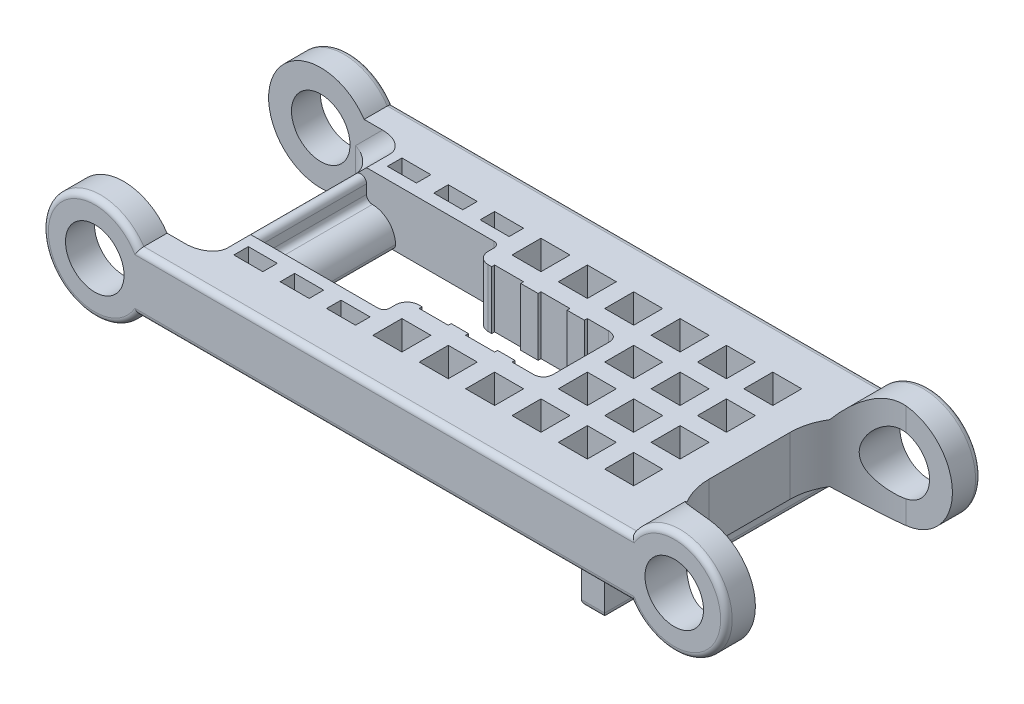
SolidWorks part; units mm, degrees
other "Markup1"
sketch "Sketch14" plane through (109, 9, 22) normal (0.0604, 0.9942, 0.0886) x (0.9982, -0.0602, -0.0054)
ref_plane "Front Plane" through (0, 0, 0) normal (0, 0, 1) x (1, 0, 0)
ref_plane "Top Plane" through (0, 0, 0) normal (0, 1, 0) x (1, 0, 0)
ref_plane "Right Plane" through (0, 0, 0) normal (1, 0, 0) x (0, 0, -1)
sketch "Sketch1" plane through (0, 0, 0) normal (0, 0, 1) x (1, 0, 0)
  line L0 (0, 0) -> (60, 0) construction
  line L1 (0, 9) -> (60, 9) construction
  line L2 (0, -9) -> (60, -9) construction
  line L3 (30, 0) -> (30, -9) construction
  line L4 (50, 5) -> (50, -5)
  line L6 (7.4833, -5) -> (7.4833, 5) construction
  line L7 (50, 5) -> (7.4833, 5)
  line L8 (50, 5) -> (50, -5)
  line L9 (50, -5) -> (7.4833, -5)
  arc A0 (0, 9) -> (0, -9) centre (0, 0) ccw construction
  arc A1 (60, -9) -> (60, 9) centre (60, 0) ccw construction
  circle A2 centre (0, 0) radius 9
  circle A3 centre (0, 0) radius 5.05
  point P3 (30, 0)
  dimension "D3" = 10.1
  dimension "D1" = 18
  dimension "D2" = 5
  dimension "D4" = 50
  dimension "D6" = 5
extrude "Boss-Extrude1" add sketch "Sketch1" along normal mid plane 44
sketch "Sketch4" plane through (0, 0, 0) normal (0, 1, 0) x (1, 0, 0)
  line L0 (-9, 22) -> (-9, -22) construction
  line L1 (9, 17) -> (-9, 17)
  line L2 (9, 17) -> (9, -17)
  line L3 (9, -17) -> (-9, -17)
  line L4 (-9, 17) -> (-9, -17)
  line L5 (9, 17) -> (-9, -17) construction
  line L6 (9, -17) -> (-9, 17) construction
  line L7 (7.4833, 22) -> (-9, 22) construction
  point P0 (0, 0)
  dimension "D1" = 5
extrude "Cut-Extrude2" cut sketch "Sketch4" against normal through all both and the other way through all
mirror "Mirror2" about plane through (50, 0, 22) normal (1, 0, 0) of "Boss-Extrude1", "Cut-Extrude2"
sketch "Sketch5" plane through (0, 5, 0) normal (0, 1, 0) x (1, 0, 0)
  line L105 (24.5, 9.5) -> (29.5, 9.5)
  line L106 (16.5, 14.5) -> (21.5, 14.5)
  line L107 (16.5, 14.5) -> (16.5, 9.5)
  line L108 (16.5, 9.5) -> (21.5, 9.5)
  line L125 (21.5, 14.5) -> (21.5, 9.5)
  line L126 (84.5, -15.5) -> (84.5, 15.5)
  line L127 (24.5, 14.5) -> (29.5, 14.5)
  line L129 (24.5, 14.5) -> (24.5, 9.5)
  line L130 (29.5, 14.5) -> (29.5, 9.5)
  line L131 (32.5, 9.5) -> (37.5, 9.5)
  line L132 (32.5, 14.5) -> (37.5, 14.5)
  line L133 (32.5, 14.5) -> (32.5, 9.5)
  line L134 (37.5, 14.5) -> (37.5, 9.5)
  line L137 (84.5, -15.5) -> (84.5, 15.5)
  line L143 (40.5, 9.5) -> (45.5, 9.5)
  line L144 (40.5, 14.5) -> (45.5, 14.5)
  line L145 (40.5, 14.5) -> (40.5, 9.5)
  line L146 (45.5, 14.5) -> (45.5, 9.5)
  line L147 (48.5, 9.5) -> (53.5, 9.5)
  line L148 (48.5, 14.5) -> (53.5, 14.5)
  line L149 (48.5, 14.5) -> (48.5, 9.5)
  line L150 (53.5, 14.5) -> (53.5, 9.5)
  line L151 (56.5, 9.5) -> (61.5, 9.5)
  line L152 (56.5, 14.5) -> (61.5, 14.5)
  line L153 (56.5, 14.5) -> (56.5, 9.5)
  line L154 (61.5, 14.5) -> (61.5, 9.5)
  line L155 (64.5, 9.5) -> (69.5, 9.5)
  line L156 (64.5, 14.5) -> (69.5, 14.5)
  line L157 (64.5, 14.5) -> (64.5, 9.5)
  line L158 (69.5, 14.5) -> (69.5, 9.5)
  line L159 (72.5, 9.5) -> (77.5, 9.5)
  line L160 (72.5, 14.5) -> (77.5, 14.5)
  line L161 (72.5, 14.5) -> (72.5, 9.5)
  line L162 (77.5, 14.5) -> (77.5, 9.5)
  line L163 (80.5, 9.5) -> (85.5, 9.5)
  line L164 (80.5, 14.5) -> (85.5, 14.5)
  line L165 (80.5, 14.5) -> (80.5, 9.5)
  line L166 (85.5, 14.5) -> (85.5, 9.5)
  line L167 (24.5, 1.5) -> (29.5, 1.5)
  line L168 (24.5, 6.5) -> (29.5, 6.5)
  line L169 (24.5, 6.5) -> (24.5, 1.5)
  line L170 (29.5, 6.5) -> (29.5, 1.5)
  line L171 (32.5, 1.5) -> (37.5, 1.5)
  line L172 (32.5, 6.5) -> (37.5, 6.5)
  line L173 (32.5, 6.5) -> (32.5, 1.5)
  line L174 (37.5, 6.5) -> (37.5, 1.5)
  line L175 (40.5, 1.5) -> (45.5, 1.5)
  line L176 (40.5, 6.5) -> (45.5, 6.5)
  line L177 (40.5, 6.5) -> (40.5, 1.5)
  line L178 (45.5, 6.5) -> (45.5, 1.5)
  line L179 (48.5, 1.5) -> (53.5, 1.5)
  line L180 (48.5, 6.5) -> (53.5, 6.5)
  line L181 (48.5, 6.5) -> (48.5, 1.5)
  line L182 (53.5, 6.5) -> (53.5, 1.5)
  line L183 (56.5, 1.5) -> (61.5, 1.5)
  line L184 (56.5, 6.5) -> (61.5, 6.5)
  line L185 (56.5, 6.5) -> (56.5, 1.5)
  line L186 (61.5, 6.5) -> (61.5, 1.5)
  line L187 (64.5, 1.5) -> (69.5, 1.5)
  line L188 (64.5, 6.5) -> (69.5, 6.5)
  line L189 (64.5, 6.5) -> (64.5, 1.5)
  line L190 (69.5, 6.5) -> (69.5, 1.5)
  line L191 (72.5, 1.5) -> (77.5, 1.5)
  line L192 (72.5, 6.5) -> (77.5, 6.5)
  line L193 (72.5, 6.5) -> (72.5, 1.5)
  line L194 (77.5, 6.5) -> (77.5, 1.5)
  line L195 (80.5, 1.5) -> (85.5, 1.5)
  line L196 (80.5, 6.5) -> (85.5, 6.5)
  line L197 (80.5, 6.5) -> (80.5, 1.5)
  line L198 (85.5, 6.5) -> (85.5, 1.5)
  line L199 (24.5, -6.5) -> (29.5, -6.5)
  line L200 (24.5, -1.5) -> (29.5, -1.5)
  line L201 (24.5, -1.5) -> (24.5, -6.5)
  line L202 (29.5, -1.5) -> (29.5, -6.5)
  line L203 (32.5, -6.5) -> (37.5, -6.5)
  line L204 (32.5, -1.5) -> (37.5, -1.5)
  line L205 (32.5, -1.5) -> (32.5, -6.5)
  line L206 (37.5, -1.5) -> (37.5, -6.5)
  line L207 (40.5, -6.5) -> (45.5, -6.5)
  line L208 (40.5, -1.5) -> (45.5, -1.5)
  line L209 (40.5, -1.5) -> (40.5, -6.5)
  line L210 (45.5, -1.5) -> (45.5, -6.5)
  line L211 (48.5, -6.5) -> (53.5, -6.5)
  line L212 (48.5, -1.5) -> (53.5, -1.5)
  line L213 (48.5, -1.5) -> (48.5, -6.5)
  line L214 (53.5, -1.5) -> (53.5, -6.5)
  line L215 (56.5, -6.5) -> (61.5, -6.5)
  line L216 (56.5, -1.5) -> (61.5, -1.5)
  line L217 (56.5, -1.5) -> (56.5, -6.5)
  line L218 (61.5, -1.5) -> (61.5, -6.5)
  line L219 (64.5, -6.5) -> (69.5, -6.5)
  line L220 (64.5, -1.5) -> (69.5, -1.5)
  line L221 (64.5, -1.5) -> (64.5, -6.5)
  line L222 (69.5, -1.5) -> (69.5, -6.5)
  line L223 (72.5, -6.5) -> (77.5, -6.5)
  line L224 (72.5, -1.5) -> (77.5, -1.5)
  line L225 (72.5, -1.5) -> (72.5, -6.5)
  line L226 (77.5, -1.5) -> (77.5, -6.5)
  line L227 (80.5, -6.5) -> (85.5, -6.5)
  line L228 (80.5, -1.5) -> (85.5, -1.5)
  line L229 (80.5, -1.5) -> (80.5, -6.5)
  line L230 (85.5, -1.5) -> (85.5, -6.5)
  line L231 (24.5, -14.5) -> (29.5, -14.5)
  line L232 (24.5, -9.5) -> (29.5, -9.5)
  line L233 (24.5, -9.5) -> (24.5, -14.5)
  line L234 (29.5, -9.5) -> (29.5, -14.5)
  line L235 (32.5, -14.5) -> (37.5, -14.5)
  line L236 (32.5, -9.5) -> (37.5, -9.5)
  line L237 (32.5, -9.5) -> (32.5, -14.5)
  line L238 (37.5, -9.5) -> (37.5, -14.5)
  line L239 (40.5, -14.5) -> (45.5, -14.5)
  line L240 (40.5, -9.5) -> (45.5, -9.5)
  line L241 (40.5, -9.5) -> (40.5, -14.5)
  line L242 (45.5, -9.5) -> (45.5, -14.5)
  line L243 (48.5, -14.5) -> (53.5, -14.5)
  line L244 (48.5, -9.5) -> (53.5, -9.5)
  line L245 (48.5, -9.5) -> (48.5, -14.5)
  line L246 (53.5, -9.5) -> (53.5, -14.5)
  line L247 (56.5, -14.5) -> (61.5, -14.5)
  line L248 (56.5, -9.5) -> (61.5, -9.5)
  line L249 (56.5, -9.5) -> (56.5, -14.5)
  line L250 (61.5, -9.5) -> (61.5, -14.5)
  line L251 (64.5, -14.5) -> (69.5, -14.5)
  line L252 (64.5, -9.5) -> (69.5, -9.5)
  line L253 (64.5, -9.5) -> (64.5, -14.5)
  line L254 (69.5, -9.5) -> (69.5, -14.5)
  line L255 (72.5, -14.5) -> (77.5, -14.5)
  line L256 (72.5, -9.5) -> (77.5, -9.5)
  line L257 (72.5, -9.5) -> (72.5, -14.5)
  line L258 (77.5, -9.5) -> (77.5, -14.5)
  line L259 (80.5, -14.5) -> (85.5, -14.5)
  line L260 (80.5, -9.5) -> (85.5, -9.5)
  line L261 (80.5, -9.5) -> (80.5, -14.5)
  line L262 (85.5, -9.5) -> (85.5, -14.5)
  line L263 (16.5, 1.5) -> (21.5, 1.5)
  line L264 (16.5, 6.5) -> (21.5, 6.5)
  line L265 (16.5, 6.5) -> (16.5, 1.5)
  line L266 (21.5, 6.5) -> (21.5, 1.5)
  line L267 (16.5, -6.5) -> (21.5, -6.5)
  line L268 (16.5, -1.5) -> (21.5, -1.5)
  line L269 (16.5, -1.5) -> (16.5, -6.5)
  line L270 (21.5, -1.5) -> (21.5, -6.5)
  line L271 (16.5, -14.5) -> (21.5, -14.5)
  line L272 (16.5, -9.5) -> (21.5, -9.5)
  line L273 (16.5, -9.5) -> (16.5, -14.5)
  line L274 (21.5, -9.5) -> (21.5, -14.5)
  line L277 (84.5, 15.5) -> (15.5, 15.5)
  line L279 (84.5, 15.5) -> (15.5, 15.5)
  line L281 (15.5, 15.5) -> (15.5, -15.5)
  line L282 (15.5, 15.5) -> (15.5, -15.5)
  line L283 (15.5, -15.5) -> (84.5, -15.5)
  line L284 (15.5, -15.5) -> (84.5, -15.5)
  dimension "D1" = 6.5
  dimension "D2" = 5
  dimension "D3" = 5
  dimension "D4" = 9
  dimension "D5" = 4
sketch "Sketch6" plane through (0, 5, 0) normal (0, 1, 0) x (1, 0, 0)
  line L6 (85, 19.5) -> (85, -21) construction
  line L7 (91, 17) -> (91, -17) construction
  line L8 (0, 0) -> (68.7415, 0) construction
  line L9 (83, 18) -> (87, 18)
  line L10 (83, 18) -> (83, 21)
  line L11 (83, 21) -> (87, 21)
  line L12 (87, 18) -> (87, 21)
  line L13 (83, 18) -> (87, 21) construction
  line L14 (83, 21) -> (87, 18) construction
  line L16 (87, -18) -> (87, -21)
  line L17 (83, -21) -> (87, -21)
  line L18 (83, -18) -> (83, -21)
  line L19 (83, -18) -> (87, -18)
  line L20 (92.5167, 22) -> (7.4833, 22) construction
  dimension "D1" = 3
  dimension "D2" = 4
  dimension "D3" = 6
  dimension "D4" = 1
extrude "Boss-Extrude2" add sketch "Sketch6" against normal blind 16
extrude "Cut-Extrude3" cut sketch "Sketch5" against normal through all
fillet "Fillet6" radius 10 2 edges at (91, 0, -17) (91, 0, 17)
sketch "Sketch13" plane through (0, 0, -18) normal (0, 0, 1) x (1, 0, 0)
  line L0 (83, -11) -> (83, -5) construction
  line L1 (83, -8) -> (87, -8)
  line L2 (83, -8) -> (83, -11)
  line L3 (83, -11) -> (87, -11)
  line L4 (87, -8) -> (87, -11)
  line L5 (83, -8) -> (87, -11) construction
  line L6 (83, -11) -> (87, -8) construction
  point P0 (85, -9.5)
  dimension "D1" = 0
  dimension "D2" = 3
extrude "Boss-Extrude5" add sketch "Sketch13" along normal up to next
sketch "Sketch16" [suppressed] plane through (0, 0, -17) normal (0, 0, 1) x (1, 0, 0)
  line L0 (100, 0) -> (100, 27.5059) construction
  line L1 (100, 27.5059) -> (100, 0) construction
  line L2 (100, 0) -> (65.6059, 0) construction
  line L3 (65.6059, 0) -> (100, 0) construction
  line L4 (100, 0) -> (70.7194, 29.2806) construction
  line L5 (70.7194, 29.2806) -> (100, 0)
  line L6 (70.7194, 29.2806) -> (66.4767, 25.038)
  line L7 (100, 0) -> (95.7574, -4.2426)
  line L8 (66.4767, 25.038) -> (95.7574, -4.2426)
  line L9 (100, 0) -> (95.7574, -4.2426)
  line L10 (100, 0) -> (106.364, -6.364)
  line L11 (95.7574, -4.2426) -> (102.1213, -10.6066)
  line L12 (106.364, -6.364) -> (102.1213, -10.6066)
  line L14 (100, 27.5059) -> (94, 27.5059)
  line L15 (100, 27.5059) -> (100, -11.8339)
  line L16 (100, -11.8339) -> (94, -11.8339)
  line L17 (94, 27.5059) -> (94, -11.8339)
  dimension "D1" = 45
  dimension "D2" = 6
  dimension "D3" = 9
  dimension "D4" = 6
sketch "Sketch17" plane through (0, 0, -17) normal (0, 0, 1) x (1, 0, 0)
  line L0 (0, 0) -> (37.5671, 37.5671) construction
  line L1 (37.5671, 37.5671) -> (0, 0) construction
  line L2 (0, 0) -> (32.9537, 0) construction
  line L3 (32.9537, 0) -> (0, 0) construction
  line L4 (0, 0) -> (0, 32.6986) construction
  line L5 (37.5671, 37.5671) -> (42.5168, 32.6173)
  line L6 (37.5671, 37.5671) -> (-6.364, -6.364)
  line L7 (42.5168, 32.6173) -> (-1.4142, -11.3137)
  line L8 (-6.364, -6.364) -> (-1.4142, -11.3137)
  dimension "D1" = 45
  dimension "D2" = 45
  dimension "D3" = 7
  dimension "D4" = 9
extrude "Cut-Extrude4" cut sketch "Sketch17" along normal up to surface (34 mm away) up to face at (5.05, 0, 17)
fillet "Fillet17" radius 3 4 edges at (11.9497, 2.0503, 17) (9, -2.9497, -17) (11.9497, 2.0503, -17) (9, -2.9497, 17)
fillet "Fillet5" radius 1 4 edges at (87, -11, 0) (83, -11, 0) (85, -11, 21) (85, -11, -21)
fillet "Fillet18" radius 1 8 edges at (109, 0, -22) (109, 0, 22) (-9, 0, 22) (-9, 0, -22) (50, -5, 22) (50, -5, -22) (50, 5, 22) (50, 5, -22)
sketch "Sketch18" plane through (0, 0, 0) normal (0, 1, 0) x (1, 0, 0)
  line L0 (14.8995, -14) -> (14.8995, 14) construction
  line L1 (14.8995, 10) -> (37.8995, 10)
  line L2 (14.8995, 10) -> (14.8995, -10)
  line L3 (14.8995, -10) -> (37.8995, -10)
  line L4 (37.8995, 10) -> (37.8995, 6)
  line L5 (14.8995, 0) -> (91, 0) construction
  line L6 (91, 7) -> (91, -7) construction
  line L7 (37.8995, 6) -> (61.8995, 6)
  line L9 (37.8995, -6) -> (61.8995, -6)
  line L10 (61.8995, 6) -> (61.8995, -6)
  line L11 (37.8995, -6) -> (37.8995, -10)
  point P13 (92.4585, 0.2294)
  dimension "D1" = 20
  dimension "D2" = 23
  dimension "D3" = 6
  dimension "D4" = 12
  dimension "D5" = 24
extrude "Cut-Extrude5" cut sketch "Sketch18" along normal through all and the other way through all
fillet "Fillet19" radius 2 6 edges at (61.5, 0, 6.5) (61.8995, 0, 6) (61.5, 0, -6.5) (61.8995, 0, -6) (37.8995, 0, -6) (37.8995, 0, 6)
sketch "Sketch19" plane through (37.5, 0, 0) normal (-1, 0, 0) x (0, 0, 1)
  line L0 (10, 5) -> (14.5, 5) construction
  line L1 (10, -5) -> (12, -5)
  line L2 (10, -5) -> (10, 5)
  line L3 (10, 5) -> (12, 5)
  line L4 (12, -5) -> (12, 5)
  line L5 (-14.5, 5) -> (-10, 5) construction
  line L6 (-10, -5) -> (-12, -5)
  line L7 (-10, -5) -> (-10, 5)
  line L8 (-10, 5) -> (-12, 5)
  line L9 (-12, -5) -> (-12, 5)
  dimension "D1" = 2
  dimension "D2" = 2
extrude "Boss-Extrude6" add sketch "Sketch19" along normal blind 22
fillet "Fillet20" radius 1 2 edges at (37.8995, 0, -10) (37.8995, 0, 10)
sketch "Sketch20" plane through (0, 0, 10) normal (0, 0, -1) x (-1, 0, 0)
  line L1 (-14.8995, -5) -> (-19.8995, -5)
  line L2 (-14.8995, -5) -> (-14.8995, 0)
  line L3 (-14.8995, 0) -> (-19.8995, 0)
  line L4 (-19.8995, -5) -> (-19.8995, 0)
  dimension "D1" = 5
  dimension "D2" = 5
extrude "Boss-Extrude7" add sketch "Sketch20" along normal up to surface (20 mm away) up to face at (25.8995, 0, -10)
fillet "Fillet21" radius 4 1 edges at (19.8995, 0, 0)
fillet "Fillet22" radius 1 3 edges at (14.8995, 5, 0) (19.8995, -5, 0) (14.8995, 0, 0)
